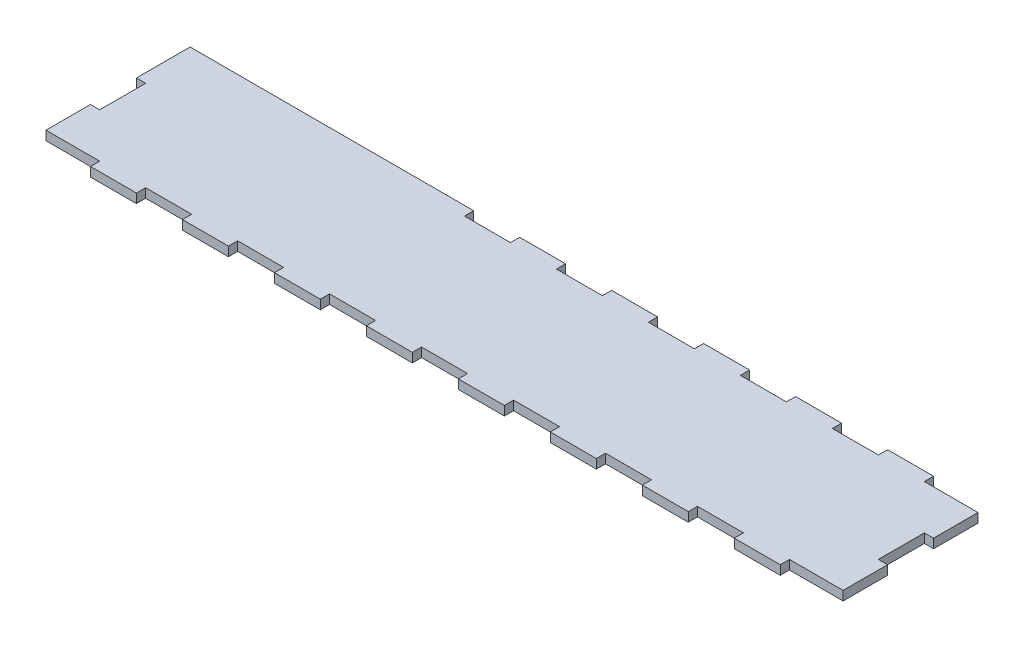
SolidWorks part; units mm, degrees
ref_plane "Alzado" through (0, 0, 0) normal (0, 0, 1) x (1, 0, 0)
ref_plane "Planta" through (0, 0, 0) normal (0, 1, 0) x (1, 0, 0)
ref_plane "Vista lateral" through (0, 0, 0) normal (1, 0, 0) x (0, 0, -1)
sketch "Croquis1" plane through (0, 0, 0) normal (0, 1, 0) x (1, 0, 0)
  line L0 (17.5, 0) -> (32.5, 0)
  line L1 (260, 3) -> (260, 17.5)
  line L2 (242.5, 50) -> (227.5, 50)
  line L3 (0, 47) -> (0, 32.5)
  line L4 (77.5, 50) -> (0, 50)
  line L5 (212.5, 50) -> (197.5, 50)
  line L6 (3, 17.5) -> (3, 32.5)
  line L7 (3, 32.5) -> (0, 32.5)
  line L8 (137.5, 47) -> (122.5, 47)
  line L9 (122.5, 47) -> (122.5, 50)
  line L10 (122.5, 50) -> (107.5, 50)
  line L11 (107.5, 50) -> (107.5, 47)
  line L12 (107.5, 47) -> (92.5, 47)
  line L13 (92.5, 47) -> (92.5, 50)
  line L14 (92.5, 50) -> (77.5, 50)
  line L15 (77.5, 50) -> (77.5, 47) construction
  line L16 (77.5, 47) -> (62.5, 47) construction
  line L17 (62.5, 47) -> (62.5, 50) construction
  line L18 (62.5, 50) -> (47.5, 50)
  line L19 (47.5, 50) -> (47.5, 47) construction
  line L20 (47.5, 47) -> (32.5, 47) construction
  line L21 (32.5, 47) -> (32.5, 50) construction
  line L22 (32.5, 50) -> (17.5, 50)
  line L23 (17.5, 50) -> (17.5, 47) construction
  line L24 (17.5, 47) -> (0, 47) construction
  line L25 (242.5, 47) -> (260, 47)
  line L26 (242.5, 50) -> (242.5, 47)
  line L27 (227.5, 47) -> (227.5, 50)
  line L28 (212.5, 47) -> (227.5, 47)
  line L29 (212.5, 50) -> (212.5, 47)
  line L30 (197.5, 47) -> (197.5, 50)
  line L31 (182.5, 47) -> (197.5, 47)
  line L32 (182.5, 50) -> (182.5, 47)
  line L33 (167.5, 47) -> (167.5, 50)
  line L34 (152.5, 47) -> (167.5, 47)
  line L35 (152.5, 50) -> (152.5, 47)
  line L36 (137.5, 47) -> (137.5, 50)
  line L37 (257, 32.5) -> (260, 32.5)
  line L38 (257, 17.5) -> (257, 32.5)
  line L39 (0, 50) -> (0, 47)
  line L40 (257, 17.5) -> (260, 17.5)
  line L41 (137.5, 3) -> (137.5, 0)
  line L42 (152.5, 0) -> (152.5, 3)
  line L43 (152.5, 3) -> (167.5, 3)
  line L44 (167.5, 3) -> (167.5, 0)
  line L45 (182.5, 0) -> (182.5, 3)
  line L46 (182.5, 3) -> (197.5, 3)
  line L47 (197.5, 3) -> (197.5, 0)
  line L48 (212.5, 0) -> (212.5, 3)
  line L49 (212.5, 3) -> (227.5, 3)
  line L50 (227.5, 3) -> (227.5, 0)
  line L51 (242.5, 0) -> (242.5, 3)
  line L52 (242.5, 3) -> (260, 3)
  line L53 (17.5, 3) -> (0, 3)
  line L54 (17.5, 0) -> (17.5, 3)
  line L55 (32.5, 3) -> (32.5, 0)
  line L56 (47.5, 3) -> (32.5, 3)
  line L57 (47.5, 0) -> (47.5, 3)
  line L58 (62.5, 3) -> (62.5, 0)
  line L59 (77.5, 3) -> (62.5, 3)
  line L60 (77.5, 0) -> (77.5, 3)
  line L61 (92.5, 3) -> (92.5, 0)
  line L62 (107.5, 3) -> (92.5, 3)
  line L63 (107.5, 0) -> (107.5, 3)
  line L64 (122.5, 3) -> (122.5, 0)
  line L65 (137.5, 3) -> (122.5, 3)
  line L66 (3, 17.5) -> (0, 17.5)
  line L67 (92.5, 50) -> (77.5, 50)
  line L68 (0, 17.5) -> (0, 3)
  line L69 (47.5, 0) -> (62.5, 0)
  line L70 (77.5, 0) -> (92.5, 0)
  line L71 (107.5, 0) -> (122.5, 0)
  line L72 (137.5, 0) -> (152.5, 0)
  line L73 (167.5, 0) -> (182.5, 0)
  line L74 (197.5, 0) -> (212.5, 0)
  line L75 (227.5, 0) -> (242.5, 0)
  line L76 (260, 32.5) -> (260, 47)
  line L77 (182.5, 50) -> (167.5, 50)
  line L78 (152.5, 50) -> (137.5, 50)
  line L79 (122.5, 50) -> (107.5, 50)
  line L80 (62.5, 50) -> (47.5, 50)
  line L81 (32.5, 50) -> (17.5, 50)
  line L82 (0, 47) -> (0.1406, 46.3229)
  dimension "D7" = 15
  dimension "D8" = 15
  dimension "D9" = 15
  dimension "D10" = 15
  dimension "D11" = 15
  dimension "D12" = 15
  dimension "D13" = 15
extrude "Saliente-Extruir1" add sketch "Croquis1" along normal blind 3 contours L35 L78 L36 L8 L9 L10 L11 L12 L13 L14 L15 L16 L17 L18 L19 L20 L21 L22 L23 L24 L3 L7 L6 L66 L68 L53 L54 L0 L55 L56 L57 L69 L58 L59 L60 L70 L61 L62 L63 L71 L64 L65 L41 L72 L42 L43 L44 L73 L45 L46 L47 region at (128.926, 0, -25.2742)
